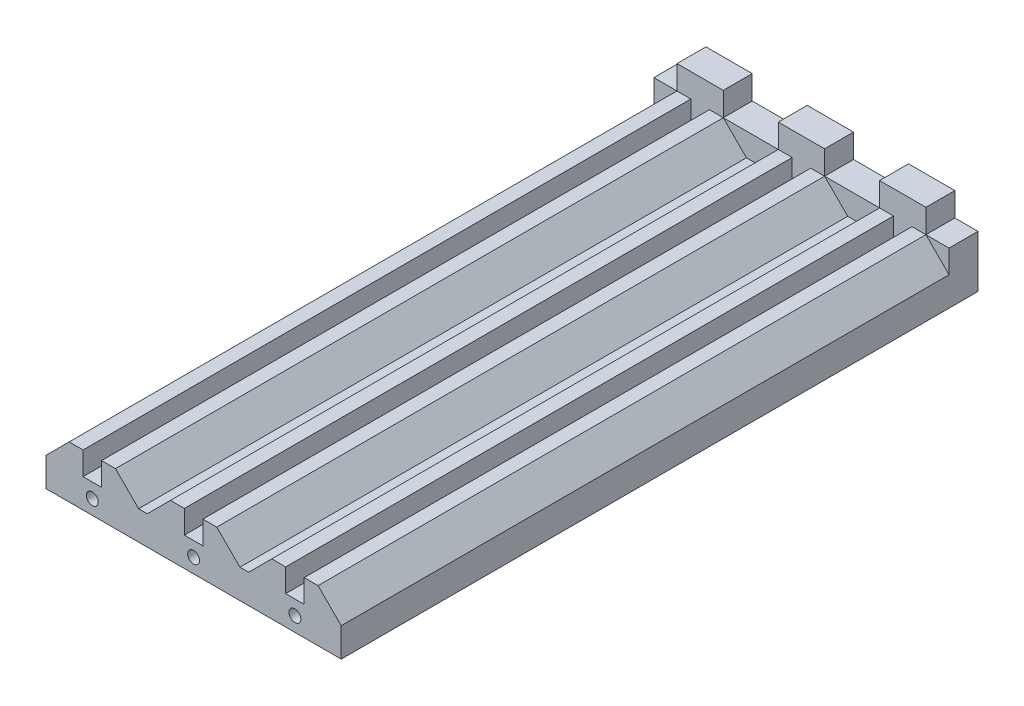
SolidWorks part; units mm, degrees
ref_plane "前视基准面" through (0, 0, 0) normal (0, 0, 1) x (1, 0, 0)
ref_plane "上视基准面" through (0, 0, 0) normal (0, 1, 0) x (1, 0, 0)
ref_plane "右视基准面" through (0, 0, 0) normal (1, 0, 0) x (0, 0, -1)
other "Configuration Table"
sketch "草图1" plane through (0, 0, 0) normal (0, 0, 1) x (1, 0, 0)
  line L0 (35, -113) -> (29, -113) construction
  line L1 (28.8, -113.2) -> (35.2, -113.2)
  line L2 (15.1626, -123.2) -> (130, -123.2)
  line L3 (15.1626, -123.2) -> (15.1626, -113.2)
  line L4 (15.1626, -113.2) -> (24, -113.2)
  line L5 (130, -123.2) -> (130, -113.2)
  line L6 (94, -105) -> (99, -105) construction
  line L8 (94, -113.2) -> (94, -105.2)
  line L9 (94, -105.2) -> (98.8, -105.2)
  line L10 (98.8, -113.2) -> (98.8, -105.2)
  line L12 (105.2, -113.2) -> (105.2, -105.2)
  line L13 (105.2, -105.2) -> (110, -105.2)
  line L14 (110, -113.2) -> (110, -105.2)
  line L15 (99, -97) -> (99, -113) construction
  line L16 (105, -113) -> (105, -97) construction
  line L17 (94, -97) -> (94, -105) construction
  line L18 (59, -113.2) -> (59, -105.2)
  line L20 (63.8, -113.2) -> (63.8, -105.2)
  line L21 (59, -105.2) -> (63.8, -105.2)
  line L22 (70.2, -113.2) -> (70.2, -105.2)
  line L24 (75, -113.2) -> (75, -105.2)
  line L25 (70.2, -105.2) -> (75, -105.2)
  line L26 (24, -113.2) -> (24, -105.2)
  line L28 (28.8, -113.2) -> (28.8, -105.2)
  line L29 (24, -105.2) -> (28.8, -105.2)
  line L30 (35.2, -113.2) -> (35.2, -105.2)
  line L32 (40, -113.2) -> (40, -105.2)
  line L33 (35.2, -105.2) -> (40, -105.2)
  line L34 (105, -97) -> (105, -8) construction
  line L35 (40, -113.2) -> (59, -113.2)
  line L38 (63.8, -113.2) -> (70.2, -113.2)
  line L39 (75, -113.2) -> (94, -113.2)
  line L41 (98.8, -113.2) -> (105.2, -113.2)
  line L42 (110, -113.2) -> (130, -113.2)
  dimension "D1" = 0.2
  dimension "D2" = 10
  dimension "D3" = 0.2
  dimension "D4" = 0.2
  dimension "D5" = 0.2
  dimension "D7" = 25
  dimension "D6" = 3
extrude "凸台-拉伸1" add sketch "草图1" against normal up to surface (170 mm away)
chamfer "倒角1" distance 8 angle 45 6 edges at (24, -113.2, -85) (110, -113.2, -85) (94, -113.2, -85) (75, -113.2, -85) (59, -113.2, -85) (40, -113.2, -85)
sketch "草图2" plane through (15.1626, 0, 0) normal (-1, 0, 0) x (0, 0, 1)
  line L4 (-170, -113.2) -> (-170, -123.2)
  line L5 (-170, -123.2) -> (0, -123.2)
  line L6 (0, -123.2) -> (0, -113.2)
  line L7 (0, -113.2) -> (-170, -113.2)
  line L8 (-170, -113.2) -> (-170, -123.2)
  line L9 (-170, -123.2) -> (0, -123.2)
  line L10 (0, -123.2) -> (0, -113.2)
  line L11 (0, -113.2) -> (-170, -113.2)
  dimension "D1" = 0
extrude "切除-拉伸1" cut sketch "草图2" against normal blind 0.84
sketch "草图3" plane through (0, 0, 0) normal (0, 0, 1) x (1, 0, 0)
  line L28 (24, -105.2) -> (16, -113.2)
  line L29 (16, -113.2) -> (16.0026, -113.2)
  line L30 (16.0026, -113.2) -> (16.0026, -123.2)
  line L31 (16.0026, -123.2) -> (130, -123.2)
  line L32 (130, -123.2) -> (130, -113.2)
  line L33 (130, -113.2) -> (118, -113.2)
  line L34 (118, -113.2) -> (110, -105.2)
  line L35 (110, -105.2) -> (105.2, -105.2)
  line L36 (105.2, -105.2) -> (105.2, -113.2)
  line L37 (105.2, -113.2) -> (98.8, -113.2)
  line L38 (98.8, -113.2) -> (98.8, -105.2)
  line L39 (98.8, -105.2) -> (94, -105.2)
  line L40 (94, -105.2) -> (86, -113.2)
  line L41 (86, -113.2) -> (83, -113.2)
  line L42 (83, -113.2) -> (75, -105.2)
  line L43 (75, -105.2) -> (70.2, -105.2)
  line L44 (70.2, -105.2) -> (70.2, -113.2)
  line L45 (70.2, -113.2) -> (63.8, -113.2)
  line L46 (63.8, -113.2) -> (63.8, -105.2)
  line L47 (63.8, -105.2) -> (59, -105.2)
  line L48 (59, -105.2) -> (51, -113.2)
  line L49 (51, -113.2) -> (48, -113.2)
  line L50 (48, -113.2) -> (40, -105.2)
  line L51 (40, -105.2) -> (35.2, -105.2)
  line L52 (35.2, -105.2) -> (35.2, -113.2)
  line L53 (35.2, -113.2) -> (28.8, -113.2)
  line L54 (28.8, -113.2) -> (28.8, -105.2)
  line L55 (28.8, -105.2) -> (24, -105.2)
  line L56 (24, -105.2) -> (16, -113.2)
  line L57 (16, -113.2) -> (16.0026, -113.2)
  line L58 (16.0026, -113.2) -> (16.0026, -123.2)
  line L59 (16.0026, -123.2) -> (130, -123.2)
  line L60 (130, -123.2) -> (130, -113.2)
  line L61 (130, -113.2) -> (118, -113.2)
  line L62 (118, -113.2) -> (110, -105.2)
  line L63 (110, -105.2) -> (105.2, -105.2)
  line L64 (105.2, -105.2) -> (105.2, -113.2)
  line L65 (105.2, -113.2) -> (98.8, -113.2)
  line L66 (98.8, -113.2) -> (98.8, -105.2)
  line L67 (98.8, -105.2) -> (94, -105.2)
  line L68 (94, -105.2) -> (86, -113.2)
  line L69 (86, -113.2) -> (83, -113.2)
  line L70 (83, -113.2) -> (75, -105.2)
  line L71 (75, -105.2) -> (70.2, -105.2)
  line L72 (70.2, -105.2) -> (70.2, -113.2)
  line L73 (70.2, -113.2) -> (63.8, -113.2)
  line L74 (63.8, -113.2) -> (63.8, -105.2)
  line L75 (63.8, -105.2) -> (59, -105.2)
  line L76 (59, -105.2) -> (51, -113.2)
  line L77 (51, -113.2) -> (48, -113.2)
  line L78 (48, -113.2) -> (40, -105.2)
  line L79 (40, -105.2) -> (35.2, -105.2)
  line L80 (35.2, -105.2) -> (35.2, -113.2)
  line L81 (35.2, -113.2) -> (28.8, -113.2)
  line L82 (28.8, -113.2) -> (28.8, -105.2)
  line L83 (28.8, -105.2) -> (24, -105.2)
  dimension "D1" = 0
extrude "凸台-拉伸2" add sketch "草图3" along normal up to surface (80 mm away)
sketch "草图4" plane through (130, 0, 0) normal (1, 0, 0) x (0, 0, -1)
  line L4 (170, -123.2) -> (170, -113.2)
  line L5 (170, -113.2) -> (-80, -113.2)
  line L6 (-80, -113.2) -> (-80, -123.2)
  line L7 (-80, -123.2) -> (170, -123.2)
  line L8 (170, -123.2) -> (170, -113.2)
  line L9 (170, -113.2) -> (-80, -113.2)
  line L10 (-80, -113.2) -> (-80, -123.2)
  line L11 (-80, -123.2) -> (170, -123.2)
  dimension "D1" = 0
extrude "切除-拉伸2" cut sketch "草图4" against normal blind 12
sketch "草图5" plane through (0, 0, -170) normal (0, 0, -1) x (-1, 0, 0)
  line L0 (-24, -105.2) -> (-28.8, -105.2) construction
  line L1 (-118, -123.2) -> (-16.0026, -123.2)
  line L2 (-118, -123.2) -> (-118, -105.2)
  line L3 (-118, -105.2) -> (-16.0026, -105.2)
  line L4 (-16.0026, -123.2) -> (-16.0026, -105.2)
  line L5 (-16.0026, -113.2) -> (-16.0026, -123.2) construction
extrude "凸台-拉伸3" add sketch "草图5" along normal blind 10
sketch "草图6" plane through (0, -123.2, 0) normal (0, -1, 0) x (1, 0, 0)
  circle A1 centre (21.0026, 25) radius 2.05
  circle A2 centre (21.0026, 25) radius 2.05
  circle A3 centre (21.0026, 0) radius 2.05
  circle A4 centre (21.0026, 0) radius 2.05
  circle A5 centre (21.0026, -57.5) radius 2.05
  circle A6 centre (21.0026, -57.5) radius 2.05
  circle A7 centre (21.0026, -82.5) radius 2.05
  circle A8 centre (21.0026, -82.5) radius 2.05
  circle A9 centre (21.0026, -140) radius 2.05
  circle A10 centre (21.0026, -140) radius 2.05
  circle A11 centre (21.0026, -165) radius 2.05
  circle A12 centre (21.0026, -165) radius 2.05
  circle A13 centre (113, -140) radius 2.05
  circle A14 centre (113, -140) radius 2.05
  circle A15 centre (113, -82.5) radius 2.05
  circle A16 centre (113, -82.5) radius 2.05
  circle A17 centre (113, -57.5) radius 2.05
  circle A18 centre (113, -57.5) radius 2.05
  circle A19 centre (113, 0) radius 2.05
  circle A20 centre (113, 0) radius 2.05
  circle A21 centre (113, 25) radius 2.05
  circle A22 centre (113, 25) radius 2.05
  circle A23 centre (113, -165) radius 2.05
  circle A24 centre (113, -165) radius 2.05
  dimension "D4" = 0
  dimension "D5" = 0
  dimension "D6" = 0
  dimension "D7" = 0
  dimension "D8" = 0
  dimension "D9" = 0
  dimension "D10" = 0
  dimension "D11" = 0
  dimension "D12" = 0
  dimension "D13" = 0
  dimension "D14" = 0
  dimension "D15" = 0
extrude "切除-拉伸3" cut sketch "草图6" against normal blind 5
sketch "草图7" plane through (0, -105.2, 0) normal (0, 1, 0) x (1, 0, 0)
  line L4 (94, 170) -> (110, 170)
  line L5 (110, 170) -> (110, 180)
  line L6 (110, 180) -> (94, 180)
  line L7 (94, 180) -> (94, 170)
  line L8 (94, 170) -> (110, 170)
  line L9 (110, 170) -> (110, 180)
  line L10 (110, 180) -> (94, 180)
  line L11 (94, 180) -> (94, 170)
  line L12 (59, 170) -> (75, 170)
  line L13 (75, 170) -> (75, 180)
  line L14 (75, 180) -> (59, 180)
  line L15 (59, 180) -> (59, 170)
  line L16 (59, 170) -> (75, 170)
  line L17 (75, 170) -> (75, 180)
  line L18 (75, 180) -> (59, 180)
  line L19 (59, 180) -> (59, 170)
  line L20 (24, 170) -> (40, 170)
  line L21 (40, 170) -> (40, 180)
  line L22 (40, 180) -> (24, 180)
  line L23 (24, 180) -> (24, 170)
  line L24 (24, 170) -> (40, 170)
  line L25 (40, 170) -> (40, 180)
  line L26 (40, 180) -> (24, 180)
  line L27 (24, 180) -> (24, 170)
  dimension "D1" = 0
  dimension "D2" = 0
  dimension "D3" = 0
extrude "凸台-拉伸4" add sketch "草图7" along normal up to vertex
sketch "草图10" plane through (0, 0, 80) normal (0, 0, 1) x (1, 0, 0)
  line L27 (16.0026, -123.2) -> (118, -123.2)
  line L28 (118, -123.2) -> (118, -113.2)
  line L29 (118, -113.2) -> (110, -105.2)
  line L30 (110, -105.2) -> (105.2, -105.2)
  line L31 (105.2, -105.2) -> (105.2, -113.2)
  line L32 (105.2, -113.2) -> (98.8, -113.2)
  line L33 (98.8, -113.2) -> (98.8, -105.2)
  line L34 (98.8, -105.2) -> (94, -105.2)
  line L35 (94, -105.2) -> (86, -113.2)
  line L36 (86, -113.2) -> (83, -113.2)
  line L37 (83, -113.2) -> (75, -105.2)
  line L38 (75, -105.2) -> (70.2, -105.2)
  line L39 (70.2, -105.2) -> (70.2, -113.2)
  line L40 (70.2, -113.2) -> (63.8, -113.2)
  line L41 (63.8, -113.2) -> (63.8, -105.2)
  line L42 (63.8, -105.2) -> (59, -105.2)
  line L43 (59, -105.2) -> (51, -113.2)
  line L44 (51, -113.2) -> (48, -113.2)
  line L45 (48, -113.2) -> (40, -105.2)
  line L46 (40, -105.2) -> (35.2, -105.2)
  line L47 (35.2, -105.2) -> (35.2, -113.2)
  line L48 (35.2, -113.2) -> (28.8, -113.2)
  line L49 (28.8, -113.2) -> (28.8, -105.2)
  line L50 (28.8, -105.2) -> (24, -105.2)
  line L51 (24, -105.2) -> (16, -113.2)
  line L52 (16, -113.2) -> (16.0026, -113.2)
  line L53 (16.0026, -113.2) -> (16.0026, -123.2)
  line L54 (16.0026, -123.2) -> (118, -123.2)
  line L55 (118, -123.2) -> (118, -113.2)
  line L56 (118, -113.2) -> (110, -105.2)
  line L57 (110, -105.2) -> (105.2, -105.2)
  line L58 (105.2, -105.2) -> (105.2, -113.2)
  line L59 (105.2, -113.2) -> (98.8, -113.2)
  line L60 (98.8, -113.2) -> (98.8, -105.2)
  line L61 (98.8, -105.2) -> (94, -105.2)
  line L62 (94, -105.2) -> (86, -113.2)
  line L63 (86, -113.2) -> (83, -113.2)
  line L64 (83, -113.2) -> (75, -105.2)
  line L65 (75, -105.2) -> (70.2, -105.2)
  line L66 (70.2, -105.2) -> (70.2, -113.2)
  line L67 (70.2, -113.2) -> (63.8, -113.2)
  line L68 (63.8, -113.2) -> (63.8, -105.2)
  line L69 (63.8, -105.2) -> (59, -105.2)
  line L70 (59, -105.2) -> (51, -113.2)
  line L71 (51, -113.2) -> (48, -113.2)
  line L72 (48, -113.2) -> (40, -105.2)
  line L73 (40, -105.2) -> (35.2, -105.2)
  line L74 (35.2, -105.2) -> (35.2, -113.2)
  line L75 (35.2, -113.2) -> (28.8, -113.2)
  line L76 (28.8, -113.2) -> (28.8, -105.2)
  line L77 (28.8, -105.2) -> (24, -105.2)
  line L78 (24, -105.2) -> (16, -113.2)
  line L79 (16, -113.2) -> (16.0026, -113.2)
  line L80 (16.0026, -113.2) -> (16.0026, -123.2)
  dimension "D1" = 0
extrude "切除-拉伸5" cut sketch "草图10" against normal blind 40
sketch "草图11" plane through (0, 0, 40) normal (0, 0, 1) x (1, 0, 0)
  line L0 (118, -123.2) -> (118, -113.2) construction
  line L1 (35.2, -113.2) -> (28.8, -113.2) construction
  line L2 (70.2, -113.2) -> (63.8, -113.2) construction
  line L3 (105.2, -113.2) -> (98.8, -113.2) construction
  circle A0 centre (32, -118.2) radius 2.05
  circle A1 centre (67, -118.2) radius 2.05
  circle A2 centre (102, -118.2) radius 2.05
  point P9 (118, -118.2)
  point P12 (32, -113.2)
  point P15 (67, -113.2)
  point P18 (102, -113.2)
  dimension "D1" = 4.1
extrude "切除-拉伸6" cut sketch "草图11" against normal blind 5
